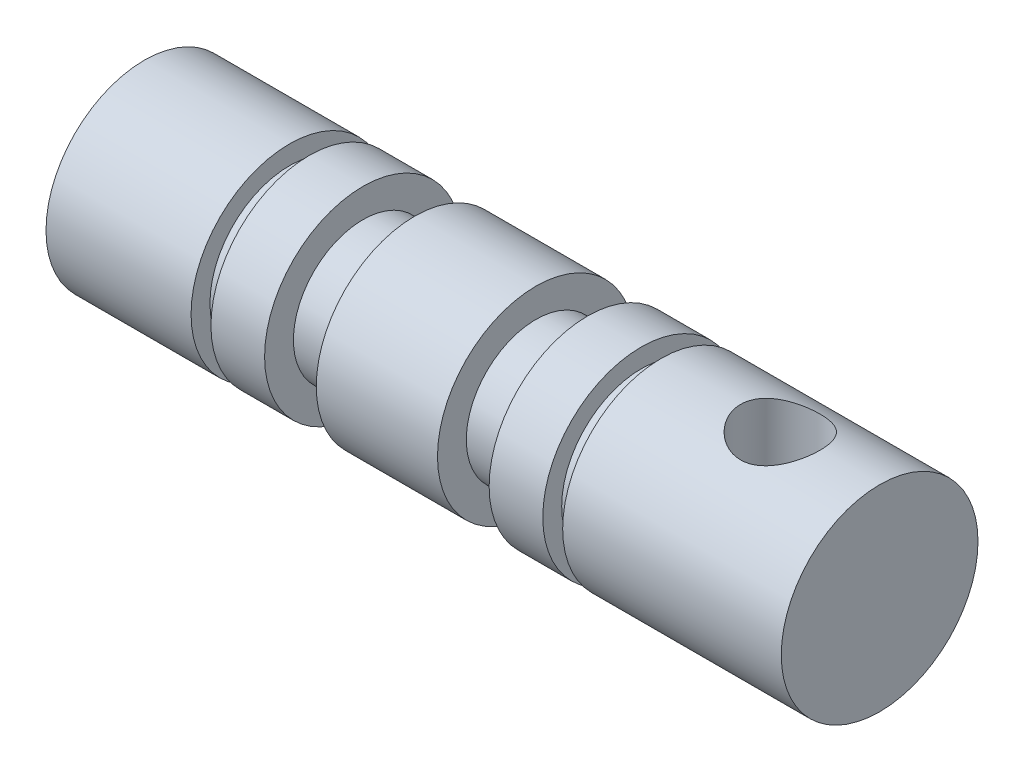
SolidWorks part; units mm, degrees
ref_plane "Спереди" through (0, 0, 0) normal (0, 0, 1) x (1, 0, 0)
ref_plane "Сверху" through (0, 0, 0) normal (0, 1, 0) x (1, 0, 0)
ref_plane "Справа" through (0, 0, 0) normal (1, 0, 0) x (0, 0, -1)
other "Configuration Table"
sketch "Эскиз1" plane through (0, 0, 0) normal (1, 0, 0) x (0, 0, -1)
  circle A0 centre (0, 0) radius 4.95
  circle A1 centre (0, 0) radius 3.5
  dimension "D1" = 9.9
  dimension "D2" = 7
extrude "Бобышка-Вытянуть1" add sketch "Эскиз1" along normal blind 37 contours A1 | A0 A1 region at (0, 0, 4.81) region at (0, 0, 0)
extrude "Вырез-Вытянуть1" cut sketch "Эскиз1<3>" along normal blind 2.6 from offset 11
sketch "Эскиз1<3>" plane through (0, 0, 0) normal (1, 0, 0) x (0, 0, -1) same geometry as "Эскиз1"
extrude "Вырез-Вытянуть2" cut sketch "Эскиз1<4>" along normal blind 2.6 from offset 19.7
sketch "Эскиз1<4>" plane through (0, 0, 0) normal (1, 0, 0) x (0, 0, -1) same geometry as "Эскиз1"
sketch "Эскиз2" plane through (0, 0, 0) normal (-1, 0, 0) x (0, 0, 1)
  circle A0 centre (0, 0) radius 1.5
  dimension "D1" = 3
extrude "Вырез-Вытянуть3" cut sketch "Эскиз2" against normal blind 10
sketch "Эскиз3" plane through (0, 0, 0) normal (0, 1, 0) x (1, 0, 0)
  line L0 (0, 4.95) -> (0, -4.95) construction
  circle A0 centre (3.3, 0) radius 1.6
  dimension "D1" = 3.2
  dimension "D2" = 3.3
extrude "Вырез-Вытянуть4" cut sketch "Эскиз3" against normal through all
sketch "Эскиз4" plane through (0, 0, 0) normal (-1, 0, 0) x (0, 0, 1)
  circle A0 centre (0, 0) radius 4
  circle A1 centre (0, 0) radius 4.95
  dimension "D1" = 8
extrude "Вырез-Вытянуть5" cut sketch "Эскиз4" along normal blind 1 from offset 8.3 offset against normal yes
extrude "Вырез-Вытянуть6" cut sketch "Эскиз4<2>" against normal blind 1 from offset 25 offset against normal yes
sketch "Эскиз4<2>" plane through (0, 0, 0) normal (-1, 0, 0) x (0, 0, 1) same geometry as "Эскиз4"
sketch "Эскиз5" plane through (0, 0, 0) normal (0, 1, 0) x (1, 0, 0)
  line L0 (37, -4.95) -> (37, 4.95) construction
  circle A0 centre (32, 0) radius 2
  dimension "D1" = 4
  dimension "D2" = 5
extrude "Вырез-Вытянуть7" cut sketch "Эскиз5" against normal through all both and the other way through all
